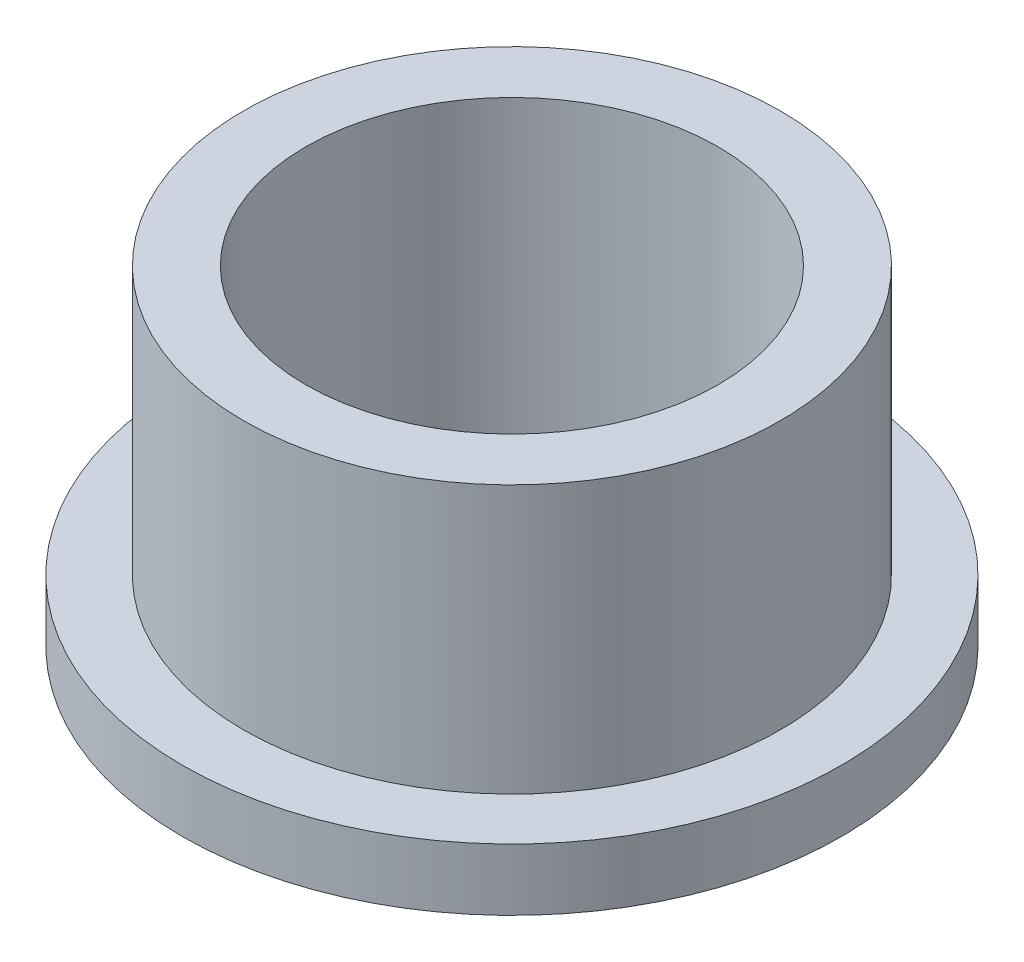
SolidWorks part; units mm, degrees
ref_plane "Front" through (0, 0, 0) normal (0, 0, 1) x (1, 0, 0)
ref_plane "Top" through (0, 0, 0) normal (0, 1, 0) x (1, 0, 0)
ref_plane "Right" through (0, 0, 0) normal (1, 0, 0) x (0, 0, -1)
sketch "Sketch1" plane through (0, 0, 0) normal (0, 1, 0) x (1, 0, 0)
  circle A0 centre (0, 0) radius 5.005
  circle A1 centre (0, 0) radius 6.515
  circle A2 centre (0, 0) radius 8
  dimension "ID" = 10.01
  dimension "OD" = 13.03
  dimension "FlangeOD" = 16
sketch "Sketch2" plane through (0, 0, 0) normal (0, 1, 0) x (1, 0, 0)
  circle A0 centre (0, 0) radius 5.005 construction
  circle A1 centre (0, 0) radius 6.515 construction
  circle A2 centre (0, 0) radius 5.005
  circle A3 centre (0, 0) radius 6.515
extrude "Boss-Extrude1" add sketch "Sketch2" along normal blind 8
sketch "Sketch3" plane through (0, 0, 0) normal (0, 1, 0) x (1, 0, 0)
  circle A0 centre (0, 0) radius 8 construction
  circle A1 centre (0, 0) radius 6.515 construction
  circle A2 centre (0, 0) radius 8
  circle A3 centre (0, 0) radius 6.515
extrude "Boss-Extrude2" add sketch "Sketch3" along normal blind 1.5
ref_axis "Center Axis 1" through (0, 8, 0) along (0, -1, 0)
